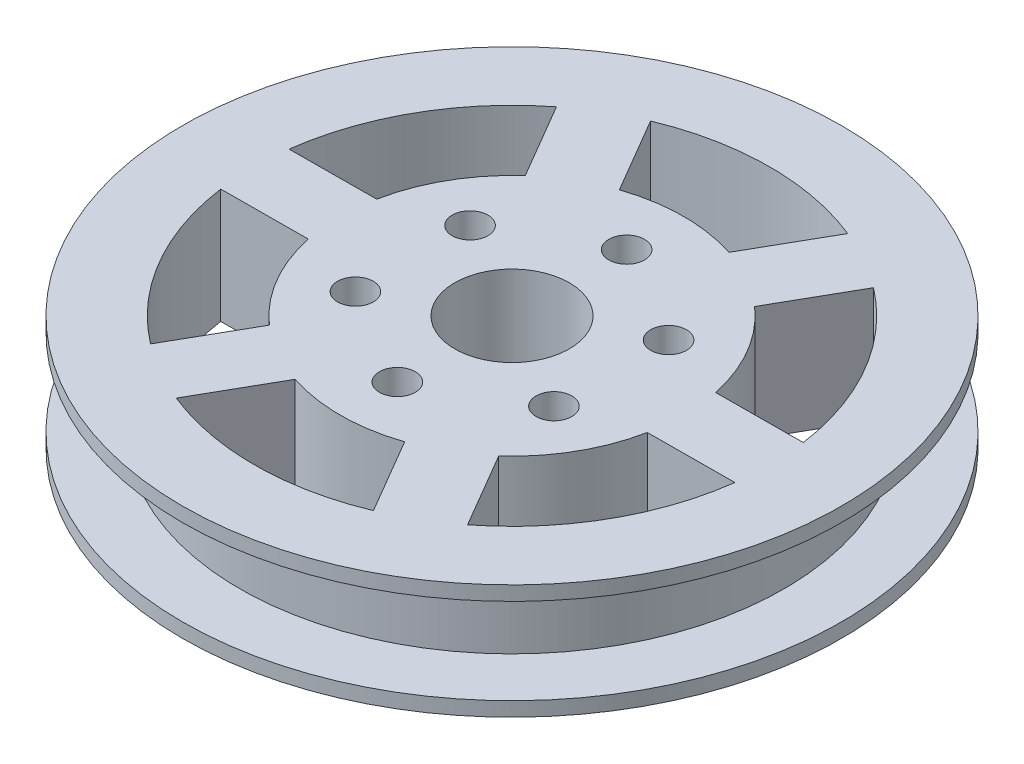
SolidWorks part; units mm, degrees
material "2024 Alloy"
ref_plane "Front Plane" through (0, 0, 0) normal (0, 0, 1) x (1, 0, 0)
ref_plane "Top Plane" through (0, 0, 0) normal (0, 1, 0) x (1, 0, 0)
ref_plane "Right Plane" through (0, 0, 0) normal (1, 0, 0) x (0, 0, -1)
sketch "Sketch2" plane through (0, 0, 0) normal (0, 1, 0) x (1, 0, 0)
  circle A0 centre (0, 0) radius 60.325
  circle A1 centre (0, 0) radius 25.4
  circle A2 centre (0, 25.4) radius 3.9688
  circle A3 centre (21.997, 12.7) radius 3.9688
  circle A4 centre (21.997, -12.7) radius 3.9688
  circle A5 centre (0, -25.4) radius 3.9688
  circle A6 centre (-21.997, -12.7) radius 3.9688
  circle A7 centre (-21.997, 12.7) radius 3.9688
  circle A8 centre (0, 0) radius 12.7
  point P19 (0, 0)
  dimension "D2" = 120.65
  dimension "D3" = 50.8
  dimension "D4" = 7.9375
  dimension "D5" = 25.4
  dimension "D1" = 6
extrude "Boss-Extrude1" add sketch "Sketch2" along normal blind 19.05 contours A0 A7 A1 A2 A3 A4 A5 A6 | A7 A1 A6 A5 A4 A3 A2 region at (-58.6188, 0, 0) region at (24.2711, 0, 4.5068)
sketch "Sketch3" plane through (0, 19.05, 0) normal (0, 1, 0) x (1, 0, 0)
  circle A0 centre (0, 25.4) radius 3.9688 construction
  circle A1 centre (21.997, 12.7) radius 3.9688 construction
  circle A2 centre (21.997, -12.7) radius 3.9688 construction
  circle A3 centre (0, -25.4) radius 3.9688 construction
  circle A4 centre (-21.997, -12.7) radius 3.9688 construction
  circle A5 centre (0, 0) radius 12.7 construction
  circle A6 centre (-21.997, 12.7) radius 3.9688 construction
  circle A7 centre (0, 25.4) radius 3.9688
  circle A8 centre (21.997, 12.7) radius 3.9688
  circle A9 centre (21.997, -12.7) radius 3.9688
  circle A10 centre (0, -25.4) radius 3.9688
  circle A11 centre (-21.997, -12.7) radius 3.9688
  circle A12 centre (0, 0) radius 12.7
  circle A13 centre (-21.997, 12.7) radius 3.9688
  circle A14 centre (0, 0) radius 73.025
  dimension "D1" = 146.05
extrude "Boss-Extrude2" add sketch "Sketch3" along normal blind 3.175
sketch "Sketch4" plane through (0, 0, 0) normal (0, -1, 0) x (1, 0, 0)
  circle A0 centre (0, 0) radius 12.7 construction
  circle A1 centre (-21.997, -12.7) radius 3.9688 construction
  circle A2 centre (0, -25.4) radius 3.9688 construction
  circle A3 centre (21.997, -12.7) radius 3.9688 construction
  circle A4 centre (21.997, 12.7) radius 3.9688 construction
  circle A5 centre (0, 25.4) radius 3.9688 construction
  circle A6 centre (-21.997, 12.7) radius 3.9688 construction
  circle A7 centre (0, 0) radius 12.7
  circle A8 centre (-21.997, -12.7) radius 3.9688
  circle A9 centre (0, -25.4) radius 3.9688
  circle A10 centre (21.997, -12.7) radius 3.9688
  circle A11 centre (21.997, 12.7) radius 3.9688
  circle A12 centre (0, 25.4) radius 3.9688
  circle A13 centre (-21.997, 12.7) radius 3.9688
  circle A14 centre (0, 0) radius 73.025 construction
  circle A15 centre (0, 0) radius 73.025
extrude "Boss-Extrude3" add sketch "Sketch4" along normal blind 3.175
sketch "Sketch6" plane through (0, 22.225, 0) normal (0, 1, 0) x (1, 0, 0)
  line L6 (-21.4095, -52.9883) -> (-11.8533, -36.2093)
  line L7 (-35.1844, 45.0353) -> (-25.4315, 28.3699)
  line L8 (-56.5939, -7.9529) -> (-37.2848, -7.8394)
  line L9 (-34.6523, -45.446) -> (-25.0961, -28.667)
  line L10 (-22.0312, 52.7328) -> (-12.2783, 36.0673)
  line L11 (-56.6836, 7.2868) -> (-37.3744, 7.4003)
  line L20 (11.8533, 36.2093) -> (21.4095, 52.9883)
  line L25 (25.0961, 28.667) -> (34.6523, 45.446)
  line L27 (37.2848, 7.8394) -> (56.5939, 7.9529)
  line L32 (37.3744, -7.4003) -> (56.6836, -7.2868)
  line L34 (25.4315, -28.3699) -> (35.1844, -45.0353)
  line L37 (12.2783, -36.0673) -> (22.0312, -52.7328)
  circle A0 centre (0, 0) radius 38.1
  circle A1 centre (0, 0) radius 57.15
  circle A3 centre (0, 0) radius 57.15
  circle A4 centre (0, 0) radius 38.1
  point P14 (0, 0)
  dimension "D1" = 76.2
  dimension "D2" = 114.3
extrude "Cut-Extrude1" cut sketch "Sketch6" against normal through all contours L20 A1 L10 | L7 A1 L11 | L8 A1 L9 | L6 A1 L37 | L34 A1 L32 | L27 A1 L25 region at (0.2791, 22.225, 47.4642) region at (-40.9656, 22.225, 23.9738) region at (41.2447, 22.225, 23.4904) region at (-41.2447, 22.225, -23.4904) region at (-0.2791, 22.225, -47.4642) region at (40.9656, 22.225, -23.9738)
